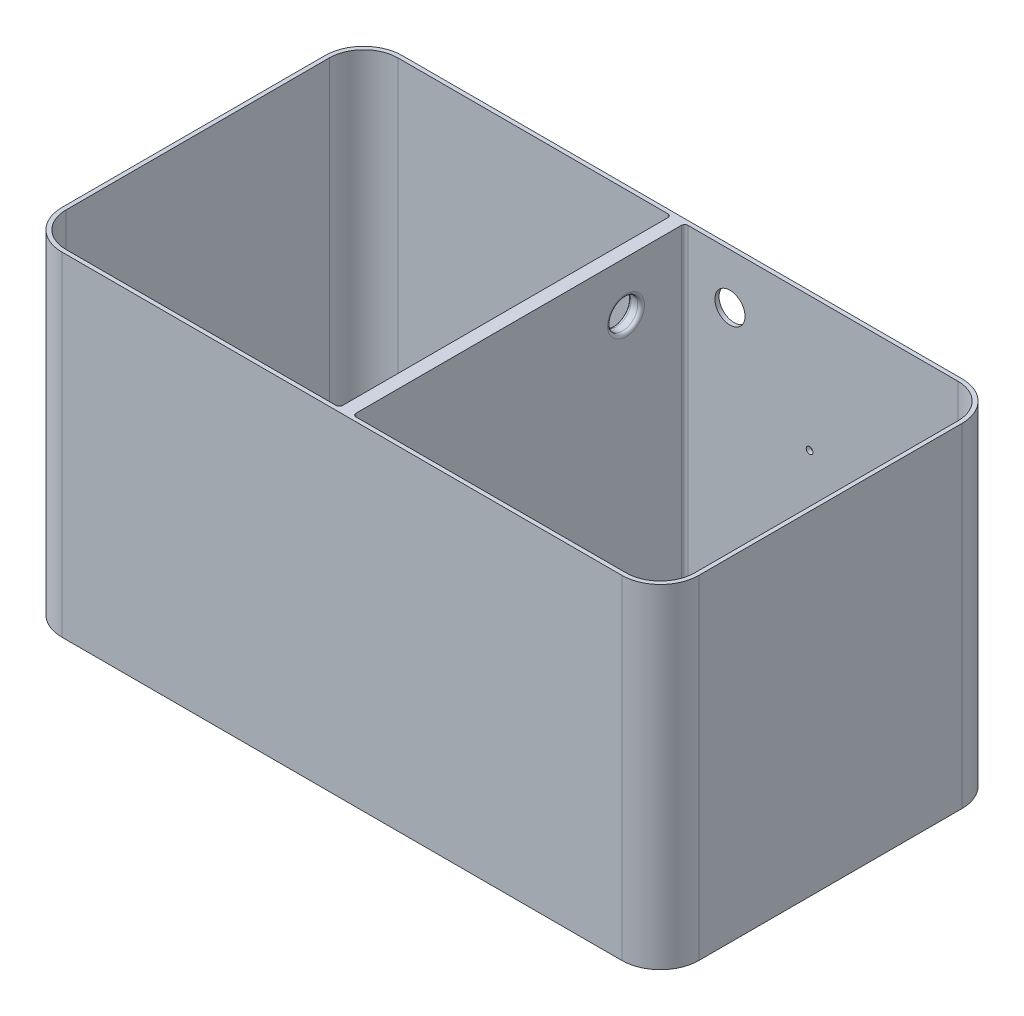
SolidWorks part; units mm, degrees
ref_plane "前视基准面" through (0, 0, 0) normal (0, 0, 1) x (1, 0, 0)
ref_plane "上视基准面" through (0, 0, 0) normal (0, 1, 0) x (1, 0, 0)
ref_plane "右视基准面" through (0, 0, 0) normal (1, 0, 0) x (0, 0, -1)
other "Configuration Table"
sketch "草图1" plane through (0, 0, 0) normal (0, 1, 0) x (1, 0, 0)
  line L1 (-167, 101.5) -> (167, 101.5)
  line L2 (-190, 78.5) -> (-190, -78.5)
  line L3 (-167, -101.5) -> (167, -101.5)
  line L4 (190, 78.5) -> (190, -78.5)
  line L5 (-190, 101.5) -> (190, -101.5) construction
  line L6 (-190, -101.5) -> (190, 101.5) construction
  arc A0 (167, -101.5) -> (190, -78.5) centre (167, -78.5) ccw
  arc A1 (167, 101.5) -> (190, 78.5) centre (167, 78.5) cw
  arc A2 (-190, -78.5) -> (-167, -101.5) centre (-167, -78.5) ccw
  arc A3 (-167, 101.5) -> (-190, 78.5) centre (-167, 78.5) ccw
  point P0 (0, 0)
  dimension "D3" = 23
  dimension "D1" = 380
  dimension "D2" = 203
extrude "凸台-拉伸1" add sketch "草图1" along normal blind 199
sketch "草图3" plane through (0, 199, 0) normal (0, 1, 0) x (1, 0, 0)
  line L0 (-190, 78.5) -> (-190, -78.5) construction
  line L1 (-167, 99) -> (167, 99)
  line L2 (-187.5, 78.5) -> (-187.5, -78.5)
  line L3 (-167, -99) -> (167, -99)
  line L4 (187.5, 78.5) -> (187.5, -78.5)
  line L5 (-187.5, 99) -> (187.5, -99) construction
  line L6 (-187.5, -99) -> (187.5, 99) construction
  line L7 (190, -78.5) -> (190, 78.5) construction
  arc A0 (-187.5, -78.5) -> (-167, -99) centre (-167, -78.5) ccw
  arc A1 (167, -99) -> (187.5, -78.5) centre (167, -78.5) ccw
  arc A2 (167, 99) -> (187.5, 78.5) centre (167, 78.5) cw
  arc A3 (-167, 99) -> (-187.5, 78.5) centre (-167, 78.5) ccw
  point P0 (0, 0)
  dimension "D5" = 20.5
  dimension "D1" = 198
  dimension "D2" = 375
  dimension "D3" = 2.5
  dimension "D4" = 2.5
extrude "切除-拉伸1" cut sketch "草图3" against normal blind 195
sketch "草图4" plane through (0, 4, 0) normal (0, 1, 0) x (1, 0, 0)
  line L0 (0, 99) -> (0, -99) construction
  line L1 (167, 99) -> (-167, 99) construction
  line L2 (-167, -99) -> (167, -99) construction
  line L3 (-4, 99) -> (-4, -99)
  line L4 (-167, -99) -> (167, -99) construction
  line L5 (4, 99) -> (4, -99)
  line L6 (-4, 99) -> (4, 99)
  line L7 (-4, -99) -> (4, -99)
  dimension "D1" = 4
extrude "凸台-拉伸2" add sketch "草图4" along normal blind 195
fillet "圆角1" radius 2 16 edges at (85.5, 4, 99) (181.4957, 4, 92.9957) (187.5, 4, 0) (181.4957, 4, -92.9957) (-85.5, 4, 99) (-181.4957, 4, 92.9957) (-187.5, 4, 0) (-181.4957, 4, -92.9957) (-4, 101.5, -99) (-4, 4, 0) (-4, 101.5, 99) (4, 101.5, 99) (4, 101.5, -99) (4, 4, 0) (85.5, 4, -99) (-85.5, 4, -99)
sketch "草图6" plane through (0, 0, -101.5) normal (0, 0, -1) x (-1, 0, 0)
  line L0 (0, 199) -> (0, 0) construction
  line L1 (-167, 199) -> (167, 199) construction
  line L2 (-6, 199) -> (-6, 0) construction
  line L4 (-167, 0) -> (167, 0) construction
  line L5 (6, 199) -> (6, 0) construction
  line L6 (-167, 199) -> (-167, 0) construction
  circle A0 centre (-155, 119) radius 2
  circle A1 centre (-155, 64) radius 2
  circle A2 centre (-78.5, 64) radius 2
  circle A3 centre (-78.5, 119) radius 2
  circle A4 centre (-31, 169) radius 9
  point P13 (-155, 119)
  point P14 (-155, 64)
  point P17 (-78.5, 119)
  point P18 (-78.5, 64)
  dimension "D5" = 4
  dimension "D6" = 4
  dimension "D7" = 4
  dimension "D8" = 4
  dimension "D10" = 18
  dimension "D1" = 12
  dimension "D2" = 12
  dimension "D3" = 76.5
  dimension "D4" = 55
  dimension "D9" = 80
  dimension "D11" = 25
  dimension "D12" = 30
extrude "切除-拉伸2" cut sketch "草图6" against normal up to next contours A2 | A3 | A0 | A1 | A4
sketch "草图7" plane through (4, 0, 0) normal (1, 0, 0) x (0, 0, -1)
  line L0 (99, 199) -> (99, 0) construction
  line L1 (78.5, 0) -> (101.5, 0) construction
  line L2 (-78.5, 199) -> (78.5, 199) construction
  circle A0 centre (64, 169) radius 9
  dimension "D2" = 18
  dimension "D1" = 35
  dimension "D3" = 30
extrude "切除-拉伸3" cut sketch "草图7" against normal up to next
fillet "圆角2" radius 2 2 edges at (-4, 169, -73) (4, 169, -73)
